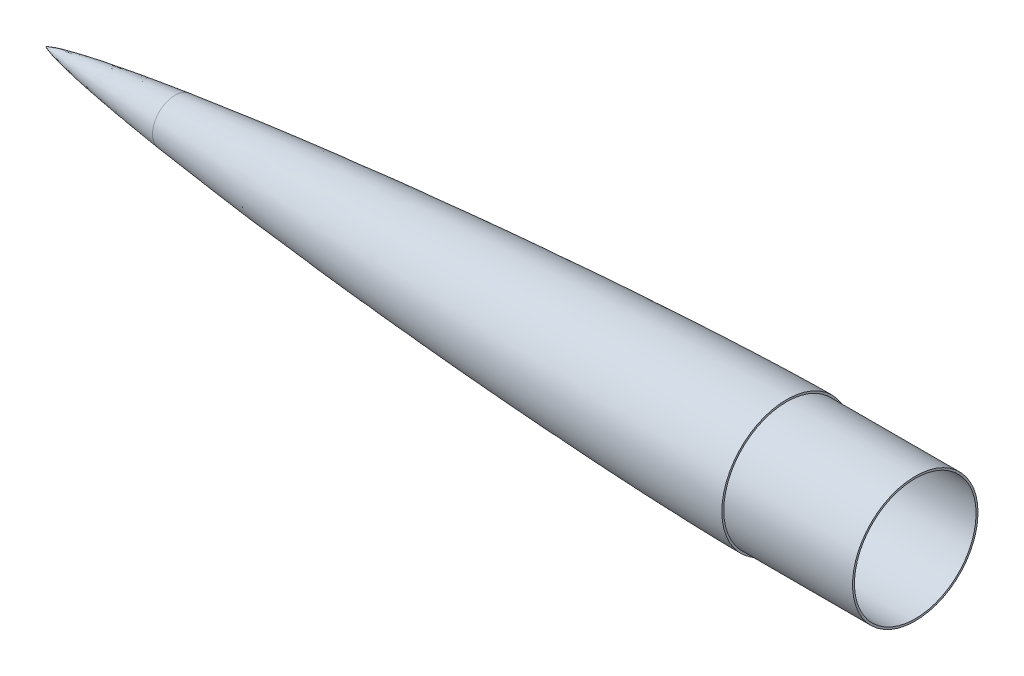
SolidWorks part; units mm, degrees
material "ABS"
ref_plane "Front Plane" through (0, 0, 0) normal (0, 0, 1) x (1, 0, 0)
ref_plane "Top Plane" through (0, 0, 0) normal (0, 1, 0) x (1, 0, 0)
ref_plane "Right Plane" through (0, 0, 0) normal (1, 0, 0) x (0, 0, -1)
sketch "Sketch1" plane through (0, 0, 0) normal (0, 0, 1) x (1, 0, 0)
  line L0 (584.3148, 51.0258) -> (0, 51.0258) construction
  line L1 (0, 0) -> (584.3148, 0) construction
  line L2 (584.3148, 0) -> (584.3148, 51.0258) construction
  line L4 (0, 0) -> (584.3148, 0)
  line L5 (584.3148, 51.0258) -> (584.3148, 0)
  spline S0 degree 4 poles (0, 0) (0.0023, 0.0055) (0.0078, 0.0161) (0.0227, 0.0347) (0.0569, 0.068) (0.1079, 0.1091) (0.1763, 0.1566) (0.2735, 0.2173) (0.3902, 0.2833) (0.5271, 0.3545) (0.6842, 0.4305) (0.9118, 0.5344) (1.2656, 0.6843) (1.8691, 0.9181) (2.9549, 1.2955) (4.9042, 1.8958) (8.4667, 2.8548) (15.1297, 4.4062) (26.8757, 6.7492) (46.5534, 10.1148) (73.3969, 14.0576) (105.7938, 18.2469) (141.5344, 22.3846) (177.3147, 26.1597) (213.1254, 29.6332) (248.9606, 32.8439) (284.8164, 35.8146) (320.6902, 38.5598) (356.58, 41.086) (392.4846, 43.3941) (428.4029, 45.4779) (464.3342, 47.3241) (495.7851, 48.7097) (522.7508, 49.7052) (544.4928, 50.3561) (559.1268, 50.706) (571.147, 50.9192) (578.6713, 51.0023) (582.4336, 51.0258) (584.3148, 51.0258) knots 0 0 0 0 0 0.000041 0.000081 0.000162 0.000324 0.000486 0.000648 0.000942 0.001237 0.001537 0.001837 0.002646 0.003853 0.005944 0.009663 0.016533 0.028972 0.052524 0.091216 0.152469 0.213722 0.274975 0.336228 0.397481 0.458734 0.519987 0.58124 0.642493 0.703745 0.764998 0.826251 0.887504 0.918131 0.948757 0.974379 0.987189 1 1 1 1 1 construction
  spline S1 degree 4 poles (0, 0) (0.0023, 0.0055) (0.0078, 0.0161) (0.0227, 0.0347) (0.0569, 0.068) (0.1079, 0.1091) (0.1763, 0.1566) (0.2735, 0.2173) (0.3902, 0.2833) (0.5271, 0.3545) (0.6842, 0.4305) (0.9118, 0.5344) (1.2656, 0.6843) (1.8691, 0.9181) (2.9549, 1.2955) (4.9042, 1.8958) (8.4667, 2.8548) (15.1297, 4.4062) (26.8757, 6.7492) (46.5534, 10.1148) (73.3969, 14.0576) (105.7938, 18.2469) (141.5344, 22.3846) (177.3147, 26.1597) (213.1254, 29.6332) (248.9606, 32.8439) (284.8164, 35.8146) (320.6902, 38.5598) (356.58, 41.086) (392.4846, 43.3941) (428.4029, 45.4779) (464.3342, 47.3241) (495.7851, 48.7097) (522.7508, 49.7052) (544.4928, 50.3561) (559.1268, 50.706) (571.147, 50.9192) (578.6713, 51.0023) (582.4336, 51.0258) (584.3148, 51.0258) knots 0 0 0 0 0 0.000041 0.000081 0.000162 0.000324 0.000486 0.000648 0.000942 0.001237 0.001537 0.001837 0.002646 0.003853 0.005944 0.009663 0.016533 0.028972 0.052524 0.091216 0.152469 0.213722 0.274975 0.336228 0.397481 0.458734 0.519987 0.58124 0.642493 0.703745 0.764998 0.826251 0.887504 0.918131 0.948757 0.974379 0.987189 1 1 1 1 1
revolve "Revolve1" add sketch "Sketch1" angle 360 about L1 region at (361.5635, 19.6649, 0)
shell "Shell1" thickness 1.524 removed face at (584.3148, 0, 51.0258)
sketch "Sketch2" plane through (584.3148, 0, 0) normal (1, 0, 0) x (0, 0, -1)
  circle A1 centre (0, 0) radius 49.5018
  circle A3 centre (0, 0) radius 47.9778
  circle A5 centre (0, 0) radius 49.5018 construction
  dimension "D1" = 1.524
extrude "Boss-Extrude1" add sketch "Sketch2" along normal blind 101.6 and the other way blind 25.4
ref_plane "Plane1" through (101.7148, 0, 0) normal (1, 0, 0) x (0, 0, -1)
split "Split1" trim tools "Plane1" bodies to split 102 resulting bodies 103 104
sketch "Sketch3" plane through (101.7148, 0, 0) normal (1, 0, 0) x (0, 0, -1)
  circle A0 centre (0, 0) radius 16.1061
extrude "Boss-Extrude2" add sketch "Sketch3" against normal up to surface
sketch "Sketch4" plane through (101.7148, 0, 0) normal (1, 0, 0) x (0, 0, -1)
  circle A0 centre (0, 0) radius 15.1019
  circle A1 centre (0, 0) radius 17.6419 construction
  dimension "D1" = 2.54
extrude "Boss-Extrude3" add sketch "Sketch4" along normal blind 12.7
sketch "Sketch5" plane through (114.4148, 0, 0) normal (1, 0, 0) x (0, 0, -1)
  point P0 (0, 0)
hole_wizard "1/4 (0.25) Diameter Hole1" positions "Sketch5" profile "Sketch6" hole size "1/4" standard "ANSI Inch"
sketch "Sketch6" plane through (114.4148, 0, 0) normal (0, 1, 0) x (0, 0, -1)
  line L0 (0, 0) -> (0, 52.7077)
  line L1 (0, 52.7077) -> (3.175, 50.8)
  line L2 (3.175, 50.8) -> (3.175, 0)
  line L5 (3.175, 0) -> (0, 0)
  line L10 (0, 52.7077) -> (-3.175, 50.8) construction
  line L11 (0, -6.35) -> (0, 107.95) construction
  dimension "Hole Dia." = 6.35
  dimension "Hole Depth" = 50.8
  dimension "Drill Angle" = 118
